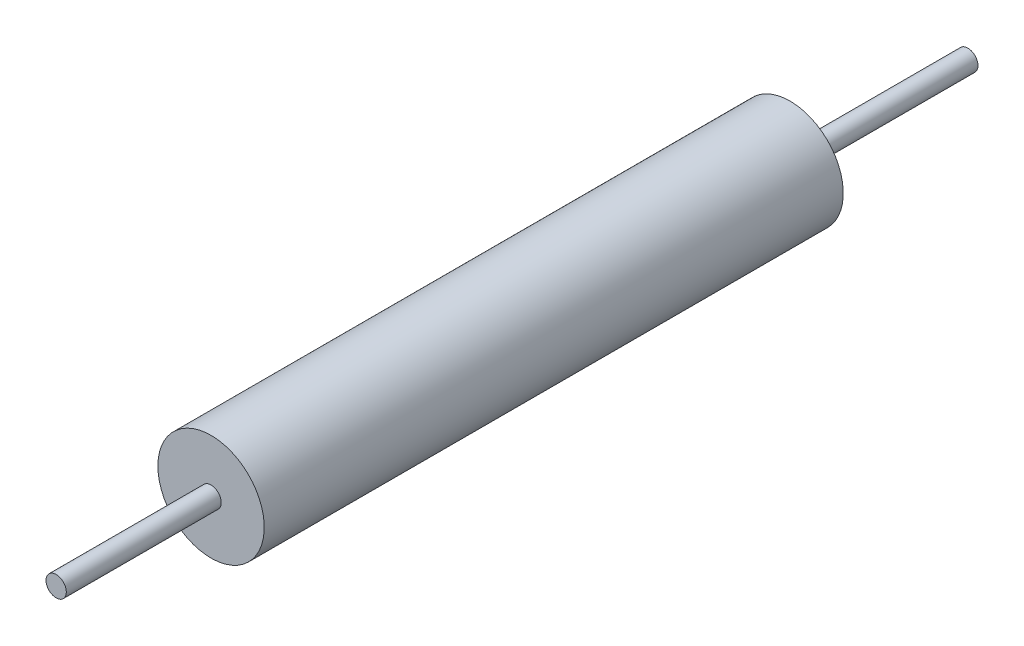
SolidWorks part; units mm, degrees
material "1060 Alloy"
ref_plane "Front Plane" through (0, 0, 0) normal (0, 0, 1) x (1, 0, 0)
ref_plane "Top Plane" through (0, 0, 0) normal (0, 1, 0) x (1, 0, 0)
ref_plane "Right Plane" through (0, 0, 0) normal (1, 0, 0) x (0, 0, -1)
sketch "Sketch1" plane through (0, 0, 0) normal (0, 0, 1) x (1, 0, 0)
  circle A0 centre (0, 0) radius 4
  circle A1 centre (0, 0) radius 3.95
  circle A2 centre (0, 0) radius 20.94
  dimension "D1" = 8
  dimension "D2" = 7.9
  dimension "D3" = 41.88
extrude "Boss-Extrude1" add sketch "Sketch1" along normal blind 228 contours A2 A0 | A0 A1 | A1 region at (-3.9887, 0, 0) region at (0, 0, 0) region at (-20.3477, 0, 0)
extrude "Boss-Extrude2" add sketch "Sketch1<3>" against normal blind 70 contours A0
sketch "Sketch1<3>" plane through (0, 0, 0) normal (0, 0, 1) x (1, 0, 0) same geometry as "Sketch1"
extrude "Boss-Extrude4" add sketch "Sketch1<5>" along normal blind 61 from surface contours A1 | A0 A1 region at (-3.9887, 0, 0) region at (0, 0, 0) starting at face at (20.94, 0, 228)
sketch "Sketch1<5>" plane through (0, 0, 0) normal (0, 0, 1) x (1, 0, 0) same geometry as "Sketch1"
